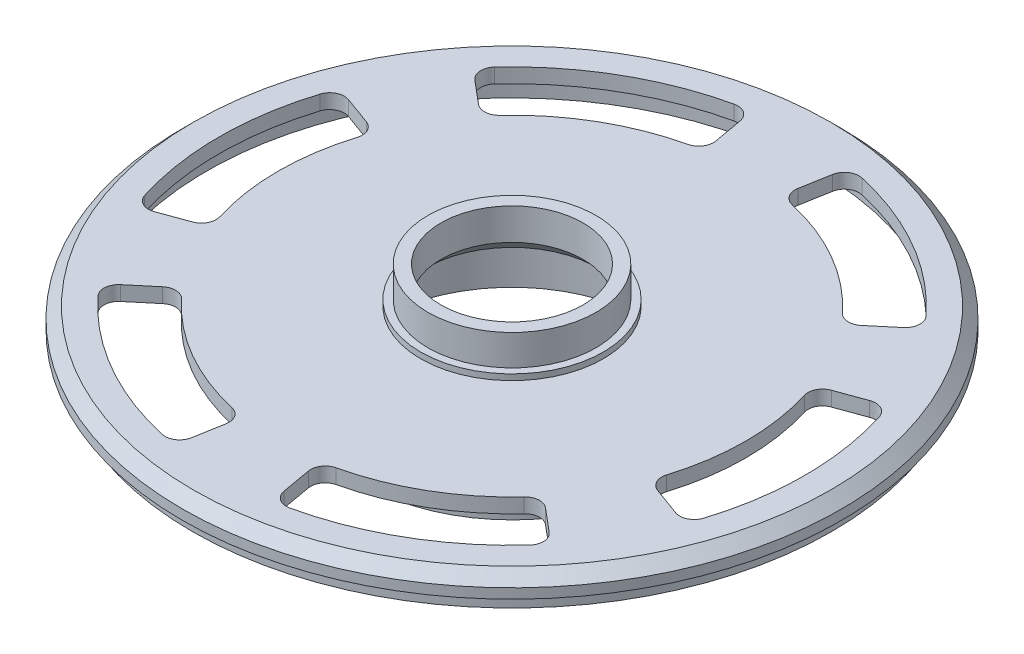
SolidWorks part; units mm, degrees
note: '?' marks a value the reader was unsure of.
ref_plane "Front Plane" through (0, 0, 0) normal (0, 0, 1) x (1, 0, 0)
ref_plane "Top Plane" through (0, 0, 0) normal (0, 1, 0) x (1, 0, 0)
ref_plane "Right Plane" through (0, 0, 0) normal (1, 0, 0) x (0, 0, -1)
ref_axis "Axis1" through (0, 0, 0) along (0, 1, 0)?
sketch "Sketch1" plane through (0, 0, 0) normal (0, 0, 1) x (1, 0, 0)
  line L0 (0, 0) -> (0, -50000) construction
  line L1 (-45.1, 8.15) -> (-43.75, 8.15)
  line L2 (45.1, 8.15) -> (-45.1, 8.15) construction
  line L3 (-43.75, 8.15) -> (-43.75, 6.15)
  line L4 (-43.75, 6.15) -> (-41.75, 6.15)
  line L5 (-41.75, 6.15) -> (-41.75, 9)
  line L6 (-41.75, 9) -> (-30.5, 9)
  line L7 (-45.1, 8.15) -> (-45.1, 9.5)
  line L8 (-43.6, 11) -> (-12.5, 11)
  line L9 (-43.8, 8.15) -> (-43.8, -6.15) construction
  line L10 (16.4229, 6.15) -> (7.6219, 6.15) construction
  line L11 (-20.5, 9) -> (-20.5, 0.15)
  line L12 (-20.5, 0.15) -> (-18.5, 0.15)
  line L13 (-18.5, 0.15) -> (-18.5, 8.15)
  line L15 (-9.73, 11.6734) -> (-9.73, 16)
  line L19 (39.5, 7.5) -> (-39.5, 7.5) construction
  line L20 (-18.5, 8.15) -> (-17.75, 8.15)
  line L23 (-11.5, 16) -> (-9.73, 16)
  line L24 (-17.75, 8.15) -> (-17.75, 9.65)
  line L25 (-17.75, 9.65) -> (-11.7534, 9.65)
  line L26 (18.25, 8.15) -> (-18.25, 8.15) construction
  line L27 (-30.5, 9) -> (-29.5, 7.5)
  line L28 (-29.5, 7.5) -> (-24.5, 7.5)
  line L29 (-24.5, 7.5) -> (-23.5, 9)
  line L30 (-23.5, 9) -> (-20.5, 9)
  line L31 (-11.7534, 9.65) -> (-9.73, 11.6734)
  line L41 (-45.1, 9.5) -> (-43.6, 11)
  line L43 (-12.5, 11) -> (-12.5, 11.8)
  line L44 (-12.5, 11.8) -> (-11.5, 11.8)
  line L45 (-9.23, 18.1) -> (-9.23, 5.85) construction
  line L46 (-11.5, 16) -> (-11.5, 11.8)
  line L47 (-18.25, 0.15) -> (18.25, 0.15) construction
  point P10 (-45.1, 11)
  point P35 (-27, 7.5)
  dimension "D1" = 0.05
  dimension "D2" = 2
  dimension "D3" = 2
  dimension "D4" = 2
  dimension "D5" = 27
  dimension "D6" = 1.5
  dimension "D7" = 0.75
  dimension "D8" = 4.2
  dimension "D9" = 1.5
  dimension "D10" = 135
  dimension "D11" = 0.5
  dimension "D12" = 5
  dimension "D13" = 7
  dimension "D14" = 1.5
  dimension "D15" = 0.8
  dimension "D16" = 1
  dimension "D19" = 23
  dimension "D20" = 37
revolve "Revolve1" add sketch "Sketch1" angle 360 about L0
sketch "Sketch2" plane through (0, 0, 0) normal (0, 1, 0) x (1, 0, 0)
  line L0 (0, 0) -> (50000, 0) construction
  line L1 (35.6692, 13.2833) -> (31.8121, 11.8794)
  line L2 (31.8121, -11.8794) -> (35.6692, -13.2833)
  arc A0 (38.2616, 12.0025) -> (38.2616, -12.0025) centre (0, 0) cw
  arc A1 (30.5846, 9.4118) -> (30.5846, -9.4118) centre (0, 0) cw
  arc A2 (38.2616, -12.0025) -> (35.6692, -13.2833) centre (36.3533, -11.4039) cw
  arc A3 (30.5846, -9.4118) -> (31.8121, -11.8794) centre (32.4962, -10) ccw
  arc A4 (38.2616, 12.0025) -> (35.6692, 13.2833) centre (36.3533, 11.4039) ccw
  arc A5 (30.5846, 9.4118) -> (31.8121, 11.8794) centre (32.4962, 10) cw
  circle A8 centre (0, 0) radius 45.1 construction
  point P11 (37.5841, -13.9802)
  point P14 (29.9723, -11.2098)
  point P17 (37.5841, 13.9802)
  point P20 (29.9723, 11.2098)
  dimension "D1" = 2
  dimension "D3" = 5
  dimension "D5" = 32
  dimension "D2" = 40
  dimension "D4" = 20
extrude "Cut-Extrude1" cut sketch "Sketch2" along normal through all and the other way through all
pattern_circular "CirPattern1" count 6 over 360 about axis through (0, 0, 0) along (0, 1, 0) of "Cut-Extrude1"
sketch "Sketch3" plane through (0, 0, 0) normal (0, 0, 1) x (1, 0, 0)
  line L0 (0, 0) -> (0, -50000) construction
  line L1 (-24.6984, 10.233) -> (-28.6984, 10.233) construction
  line L2 (-29.1, 10.233) -> (-24.9, 10.233)
  line L3 (-29.1, 10.233) -> (-29.1, 7.2084)
  line L4 (-29.1, 7.2084) -> (-24.9, 7.2084)
  line L5 (-24.9, 10.233) -> (-24.9, 7.2084)
  point P7 (-27, 10.233)
  dimension "D1" = 27
  dimension "D2" = 4.2
revolve "Cut-Revolve1" [suppressed] cut sketch "Sketch3" angle 360 about L0
sketch "Sketch4" plane through (0, 0, 0) normal (0, 1, 0) x (1, 0, 0)
  circle A0 centre (27, 0) radius 2.06
  dimension "D1" = 4.12
  dimension "D2" = 27
extrude "Cut-Extrude3" cut sketch "Sketch4" against normal through all from surface at 10.233
pattern_circular "CirPattern2" count 42 over 360 about axis through (0, 0, 0) along (0, 1, 0) of "Cut-Extrude3"
sketch "Sketch5" plane through (0, 7.5, 0) normal (0, -1, 0) x (1, 0, 0)
  circle A0 centre (0, 0) radius 27
extrude "Cut-Extrude-Thin1" cut sketch "Sketch5" against normal up to surface (2.733 mm away) thin thin type mid plane wall 2
